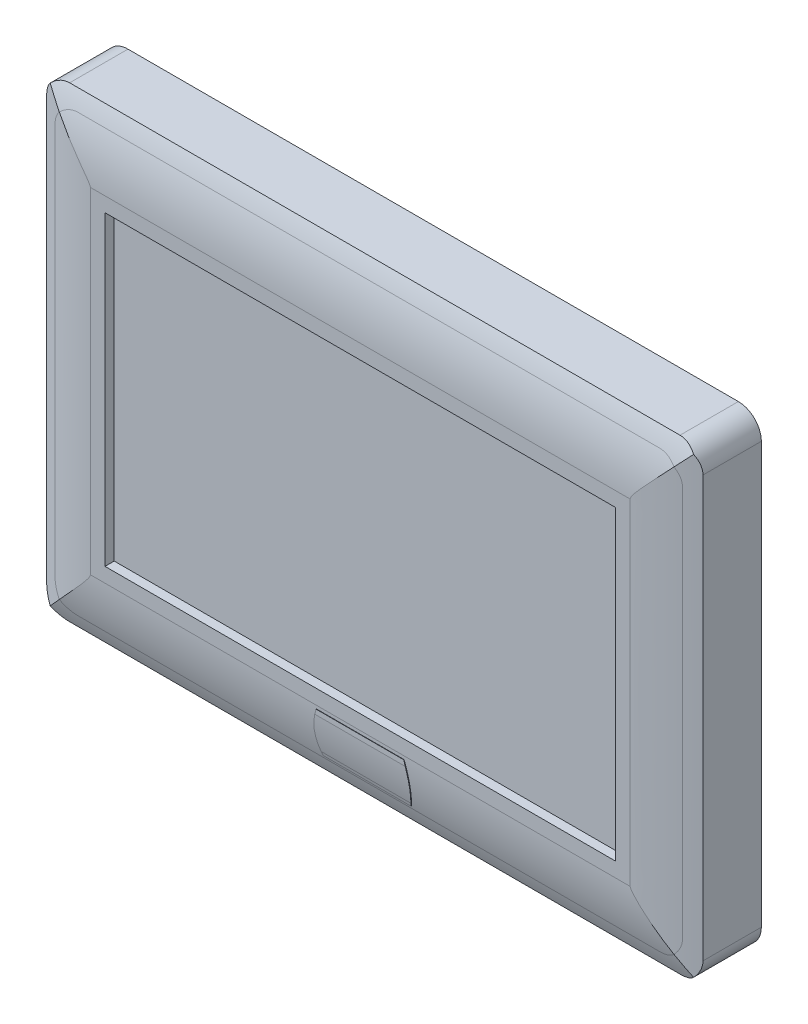
SolidWorks part; units mm, degrees
ref_plane "Front Plane" through (0, 0, 0) normal (0, 0, 1) x (1, 0, 0)
ref_plane "Top Plane" through (0, 0, 0) normal (0, 1, 0) x (1, 0, 0)
ref_plane "Right Plane" through (0, 0, 0) normal (1, 0, 0) x (0, 0, -1)
sketch "Sketch1" plane through (0, 0, 0) normal (0, 0, 1) x (1, 0, 0)
  line L1 (142.875, -101.6) -> (-142.875, -101.6)
  line L2 (142.875, -101.6) -> (142.875, 101.6)
  line L3 (142.875, 101.6) -> (-142.875, 101.6)
  line L4 (-142.875, -101.6) -> (-142.875, 101.6)
  line L5 (142.875, -101.6) -> (-142.875, 101.6) construction
  line L6 (142.875, 101.6) -> (-142.875, -101.6) construction
  point P0 (0, 0)
  dimension "D1" = 285.75
  dimension "D2" = 203.2
extrude "Boss-Extrude1" add sketch "Sketch1" along normal mid plane 31.75
sketch "Sketch2" plane through (0, 0, 0) normal (1, 0, 0) x (0, 0, -1)
  line L1 (15.875, -101.6) -> (15.875, 101.6) construction
  line L3 (15.875, -76.2) -> (17.8232, -76.2)
  line L4 (15.875, 76.2) -> (15.875, -76.2)
  line L5 (15.875, 76.2) -> (23.0314, -61.2021)
  arc A0 (23.0314, -61.2021) -> (17.8232, -76.2) centre (25.4, -70.4279) ccw
  dimension "D1" = 19.05
extrude "Boss-Extrude3" add sketch "Sketch2" along normal mid plane 134.9375 contours A0 L5 L4 | A0 L4 L3 region at (0, -74.7882, -16.4476) region at (0, -17.011, -18.2431)
sketch "Sketch3" plane through (0, 0, 15.875) normal (0, 0, 1) x (1, 0, 0)
  line L1 (111.125, -66.675) -> (-111.125, -66.675)
  line L2 (111.125, -66.675) -> (111.125, 66.675)
  line L3 (111.125, 66.675) -> (-111.125, 66.675)
  line L4 (-111.125, -66.675) -> (-111.125, 66.675)
  line L5 (111.125, -66.675) -> (-111.125, 66.675) construction
  line L6 (111.125, 66.675) -> (-111.125, -66.675) construction
  point P0 (0, 0)
  dimension "D1" = 222.25
  dimension "D2" = 133.35
extrude "Cut-Extrude1" cut sketch "Sketch3" against normal blind 4
sketch "Sketch4" plane through (0, 0, 0) normal (1, 0, 0) x (0, 0, -1)
  line L3 (-15.875, -101.6) -> (-15.875, 101.6) construction
  line L4 (-15.875, 101.6) -> (-9.525, 101.6)
  line L5 (-15.875, 101.6) -> (15.875, 101.6) construction
  line L6 (-15.875, 101.6) -> (-15.875, 73.025)
  spline S0 degree 2 poles (-15.875, 73.025) (-15.74, 87.6604) (-9.525, 101.6) knots 0 0 0 1 1 1
  dimension "D1" = 6.35
extrude "Cut-Extrude2" cut sketch "Sketch4" against normal mid plane 300
sketch "Sketch5" plane through (0, 0, 0) normal (0, 1, 0) x (1, 0, 0)
  line L2 (-142.875, -15.875) -> (-142.875, -9.525)
  line L3 (-142.875, -15.875) -> (-117.475, -15.875)
  line L4 (-142.875, -15.875) -> (142.875, -15.875) construction
  spline S0 degree 2 poles (-117.475, -15.875) (-130.5576, -15.4109) (-142.875, -9.525) knots 0 0 0 1 1 1
extrude "Cut-Extrude3" cut sketch "Sketch5" against normal mid plane 220
mirror "Mirror1" about plane through (0, 0, 0) normal (1, 0, 0) of "Cut-Extrude3"
mirror "Mirror2" about plane through (0, 0, 0) normal (0, 1, 0) of "Cut-Extrude2"
fillet "Fillet1" radius 10 4 edges at (-142.875, -101.6, -3.175) (-142.875, 101.6, -3.175) (142.875, 101.6, -3.175) (142.875, -101.6, -3.175)
ref_plane "Plane1" through (0, 0, 20) normal (0, 0, 1) x (1, 0, 0)
sketch "Sketch6" plane through (0, 0, 20) normal (0, 0, 1) x (1, 0, 0)
  line L2 (-136.6326, 84.9161) -> (-136.6326, -84.9161)
  line L4 (-126.6326, -94.9161) -> (126.6326, -94.9161)
  line L6 (136.6326, -84.9161) -> (136.6326, 84.9161)
  line L8 (126.6326, 94.9161) -> (-126.6326, 94.9161)
  arc A0 (136.6326, 84.9161) -> (126.6326, 94.9161) centre (126.6326, 84.9161) ccw
  arc A1 (-136.6326, -84.9161) -> (-126.6326, -94.9161) centre (-126.6326, -84.9161) ccw
  arc A2 (136.6326, -84.9161) -> (126.6326, -94.9161) centre (126.6326, -84.9161) cw
  arc A3 (-136.6326, 84.9161) -> (-126.6326, 94.9161) centre (-126.6326, 84.9161) cw
  spline S2 degree 3 poles (-140.0461, 98.5696) (-138.1541, 96.5438) (-136.2442, 94.5006) (-132.3901, 90.3768) (-130.4503, 88.3015) (-127.532, 85.1674) (-126.5576, 84.1189) (-124.609, 82.011) (-123.6355, 80.9532) (-122.1862, 79.3534) (-121.7049, 78.8178) (-120.7505, 77.738) (-120.2771, 77.1941) (-119.351, 76.0866) (-118.8968, 75.5255) (-118.2716, 74.6435) (-118.0726, 74.3427) (-117.7196, 73.7083) (-117.5669, 73.3783) (-117.475, 73.025) knots 0 0 0 0 0.25 0.25 0.5 0.5 0.625 0.625 0.75 0.75 0.8125 0.8125 0.875 0.875 0.9375 0.9375 0.96875 0.96875 1 1 1 1 construction
  spline S3 degree 3 poles (-117.475, -73.025) (-117.5682, -73.3833) (-117.7203, -73.7093) (-118.0693, -74.3371) (-118.2678, -74.638) (-118.6857, -75.228) (-118.9054, -75.5164) (-119.3531, -76.0834) (-119.5818, -76.3626) (-120.2758, -77.1926) (-120.749, -77.7362) (-121.703, -78.8157) (-122.1843, -79.3512) (-123.6337, -80.9512) (-124.6079, -82.0098) (-126.5561, -84.1173) (-127.5304, -85.1657) (-130.4487, -88.2997) (-132.3886, -90.3752) (-136.2435, -94.4998) (-138.1538, -96.5434) (-140.0461, -98.5696) knots 0 0 0 0 0.03125 0.03125 0.0625 0.0625 0.09375 0.09375 0.125 0.125 0.1875 0.1875 0.25 0.25 0.375 0.375 0.5 0.5 0.75 0.75 1 1 1 1 construction
  spline S4 degree 3 poles (117.475, -73.025) (117.5682, -73.3833) (117.7203, -73.7093) (118.0693, -74.3371) (118.2678, -74.638) (118.6857, -75.228) (118.9054, -75.5164) (119.3531, -76.0834) (119.5818, -76.3626) (120.2758, -77.1926) (120.749, -77.7362) (121.703, -78.8157) (122.1843, -79.3512) (123.6337, -80.9512) (124.6079, -82.0098) (126.5561, -84.1173) (127.5304, -85.1657) (130.4487, -88.2997) (132.3886, -90.3752) (136.2435, -94.4998) (138.1538, -96.5434) (140.0461, -98.5696) knots 0 0 0 0 0.03125 0.03125 0.0625 0.0625 0.09375 0.09375 0.125 0.125 0.1875 0.1875 0.25 0.25 0.375 0.375 0.5 0.5 0.75 0.75 1 1 1 1 construction
  spline S5 degree 3 poles (140.0461, 98.5696) (138.1541, 96.5438) (136.2442, 94.5006) (132.3901, 90.3768) (130.4503, 88.3015) (127.532, 85.1674) (126.5576, 84.1189) (124.609, 82.011) (123.6355, 80.9532) (122.1862, 79.3534) (121.7049, 78.8178) (120.7505, 77.738) (120.2771, 77.1941) (119.351, 76.0866) (118.8968, 75.5255) (118.2716, 74.6435) (118.0726, 74.3427) (117.7196, 73.7083) (117.5669, 73.3783) (117.475, 73.025) knots 0 0 0 0 0.25 0.25 0.5 0.5 0.625 0.625 0.75 0.75 0.8125 0.8125 0.875 0.875 0.9375 0.9375 0.96875 0.96875 1 1 1 1 construction
  point P4 (0, 0)
  point P15 (136.6326, 94.9161)
  point P18 (-136.6326, -94.9161)
  point P21 (136.6326, -94.9161)
  point P24 (-136.6326, 94.9161)
  dimension "D1" = 10
split line "Split Line1"
sketch "Sketch7" plane through (0, 0, 20) normal (0, 0, 1) x (1, 0, 0)
  line L4 (19.05, -74.4456) -> (-19.05, -74.4456)
  line L5 (19.05, -93.4956) -> (-19.05, -93.4956)
  spline S0 degree 2 poles (-19.05, -74.4456) (-22.225, -83.9706) (-19.05, -93.4956) knots 0 0 0 1 1 1
  spline S1 degree 2 poles (19.05, -74.4456) (22.225, -83.9706) (19.05, -93.4956) knots 0 0 0 1 1 1
  point P12 (0, -83.9706)
extrude "Cut-Extrude5" cut sketch "Sketch7" against normal blind 8
sketch "Sketch8" plane through (0, 0, 12) normal (0, 0, 1) x (1, 0, 0)
  line L2 (19.05, -74.4456) -> (-19.05, -74.4456)
  line L3 (-19.05, -93.4956) -> (19.05, -93.4956)
  line L4 (19.05, -74.4456) -> (-19.05, -74.4456)
  line L5 (-19.05, -93.4956) -> (19.05, -93.4956)
  parabola Q2 (19.05, -93.4956) -> (19.05, -74.4456) focus (6.35, -83.9706) apex (20.6375, -83.9706)
  parabola Q3 (-19.05, -74.4456) -> (-19.05, -93.4956) focus (-6.35, -83.9706) apex (-20.6375, -83.9706)
  parabola Q4 (19.05, -93.4956) -> (19.05, -74.4456) focus (6.35, -83.9706) apex (20.6375, -83.9706)
  parabola Q5 (-19.05, -74.4456) -> (-19.05, -93.4956) focus (-6.35, -83.9706) apex (-20.6375, -83.9706)
  dimension "D1" = 0
extrude "Boss-Extrude4" add sketch "Sketch8" along normal blind 4
sketch "Sketch9" plane through (0, 0, 0) normal (1, 0, 0) x (0, 0, -1)
  line L0 (-16, -74.4456) -> (-16, -93.4956) construction
  line L1 (-16, -74.4456) -> (-16, -93.4956)
  line L2 (-16, -93.4956) -> (-12.8682, -93.4956)
  parabola Q0 (-15.875, -73.025) -> (-13.093, -91.8875) focus (18.9694, -76.3628) apex (-15.4275, -80.2992) construction
  parabola Q1 (-15.875, -73.025) -> (-13.093, -91.8875) focus (18.9694, -76.3628) apex (-15.4275, -80.2992)
  parabola Q2 (-13.093, -91.8875) -> (-10.801, -98.5696) focus (18.9694, -76.3628) apex (-15.4275, -80.2992) construction
  parabola Q3 (-13.093, -91.8875) -> (-10.801, -98.5696) focus (18.9694, -76.3628) apex (-15.4275, -80.2992)
  spline S0 degree 1 poles (-16.125, -73.0273) (-13.3331, -91.9571) knots 0 0 1 1 construction
  spline S1 degree 1 poles (-13.3331, -91.9571) (-11.0334, -98.6617) knots 0 0 1 1 construction
  spline S2 degree 3 poles (-16.125, -73.0273) (-16.1167, -73.9236) (-16.0742, -75.4262) (-15.8813, -78.6109) (-15.455, -82.4773) (-14.5767, -87.2831) (-13.7813, -90.4126) (-13.3331, -91.9571) knots 0.499691 0.499691 0.499691 0.499691 0.499805 0.49988 0.500096 0.500298 0.5005 0.5005 0.5005 0.5005
  spline S3 degree 3 poles (-13.3331, -91.9571) (-13.2208, -92.3439) (-13.0296, -92.9832) (-12.6771, -94.1048) (-12.0629, -95.9567) (-11.4712, -97.5575) (-11.0334, -98.6617) knots 0.5005 0.5005 0.5005 0.5005 0.500551 0.500584 0.500647 0.500794 0.500794 0.500794 0.500794
  point P16 (-16, -76.6192)
  dimension "D1" = 0.25
extrude "Cut-Extrude6" cut sketch "Sketch9" against normal through all and the other way through all contours S3 S2 L1 L2 region at (0, -88.6931, 15.0482)
sketch "Sketch10" plane through (0, 0, 15.875) normal (0, 0, 1) x (1, 0, 0)
  line L0 (0, 127.8913) -> (0, -130.0725) construction
  line L1 (-32.7762, 76.7259) -> (-22.7423, 91.7008)
  line L2 (-22.7423, 91.7008) -> (-16.94, 91.7008)
  line L3 (-16.94, 91.7008) -> (-13.579, 83.0395)
  line L4 (-11.346, 77.2848) -> (-10.6109, 81.7169)
  line L5 (-8.955, 91.7008) -> (-4.3593, 91.7008)
  line L6 (-4.3593, 91.7008) -> (0.206, 86.7165)
  line L7 (0.206, 86.7165) -> (6.418, 91.7008)
  line L8 (6.418, 91.7008) -> (17.8276, 91.7008)
  line L9 (17.8276, 91.7008) -> (21.1075, 87.8249)
  line L10 (21.1075, 87.8249) -> (25.651, 91.7008)
  line L11 (25.651, 91.7008) -> (32.7491, 91.7008)
  line L12 (32.7491, 91.7008) -> (26.3689, 86.2582)
  line L13 (15.5383, 86.1417) -> (10.9922, 91.3297)
  line L14 (10.9922, 91.3297) -> (10.0785, 85.8912)
  line L15 (8.6686, 77.4987) -> (16.225, 83.7983)
  line L16 (24.6284, 83.8772) -> (30.952, 76.7259)
  line L17 (30.952, 76.7259) -> (23.7958, 76.7259)
  line L18 (23.7958, 76.7259) -> (20.0485, 81.0626)
  line L19 (20.0485, 81.0626) -> (14.9601, 76.7259)
  line L20 (14.9601, 76.7259) -> (3.0843, 76.7259)
  line L21 (3.0843, 76.7259) -> (4.1776, 83.2967)
  line L22 (-5.965, 76.7259) -> (-5.0094, 82.4643)
  line L23 (-5.965, 76.7259) -> (-17.0392, 76.7259)
  line L24 (-17.0392, 76.7259) -> (-18.332, 80.3298)
  line L25 (-20.5714, 86.613) -> (-19.2512, 82.9069)
  line L26 (-19.2512, 82.9069) -> (-22.923, 82.9069)
  line L27 (-22.923, 82.9069) -> (-20.5714, 86.613)
  line L28 (-12.926, 81.3565) -> (-11.346, 77.2848)
  line L29 (-10.2878, 83.6648) -> (-8.955, 91.7008)
  line L30 (9.6936, 83.5998) -> (8.6686, 77.4987)
  line L31 (26.3689, 86.2582) -> (24.6284, 83.8772)
  spline S0 degree 2 poles (-32.7762, 76.7259) (-26.0108, 79.9434) (-18.8613, 81.8138) knots 0 0 0 0.245002 0.245002 0.245002
  spline S1 degree 3 poles (-32.7762, 76.7259) (-26.2264, 78.4871) (-19.6314, 80.2492) (-12.926, 81.3565) knots 0 0 0 0 0.351138 0.351138 0.351138 0.351138
  spline S2 degree 2 poles (26.3689, 86.2582) (20.9508, 86.3279) (15.5383, 86.1417) knots 0 0 0 0.495892 0.495892 0.495892
  spline S3 degree 3 poles (-4.6661, 84.5342) (-1.6063, 84.9457) (1.4673, 85.2641) (4.5464, 85.5132) knots 0.484673 0.484673 0.484673 0.484673 0.638107 0.638107 0.638107 0.638107
  spline S4 degree 3 poles (-4.6661, 84.5342) (-9.4424, 83.8872) (-14.1952, 83.0326) (-18.8613, 81.8138) knots 0 0 0 0 1 1 1 1
  spline S5 degree 2 poles (10.0785, 85.8912) (7.3105, 85.7329) (4.5464, 85.5132) knots 0.746128 0.746128 0.746128 1 1 1
  spline S6 degree 2 poles (16.2207, 83.7947) (20.427, 83.8796) (24.6284, 83.8772) knots 0.85515 0.85515 0.85515 1 1 1
  spline S7 degree 3 poles (-10.6109, 81.7169) (-8.7474, 81.9929) (-3.8325, 82.6565) (2.9419, 83.2552) (7.853, 83.5162) (9.6926, 83.5941) knots 0.391487 0.391487 0.391487 0.391487 0.488807 0.647668 0.742736 0.742736 0.742736 0.742736
